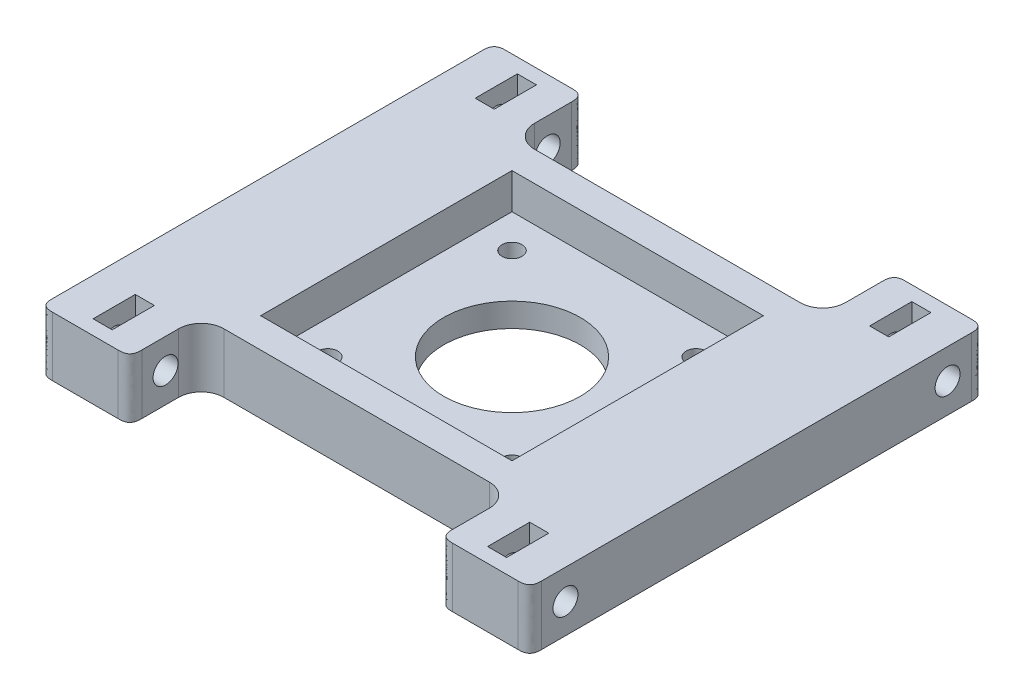
SolidWorks part; units mm, degrees
ref_plane "Front Plane" through (0, 0, 0) normal (0, 0, 1) x (1, 0, 0)
ref_plane "Top Plane" through (0, 0, 0) normal (0, 1, 0) x (1, 0, 0)
ref_plane "Right Plane" through (0, 0, 0) normal (1, 0, 0) x (0, 0, -1)
sketch "Sketch1" plane through (0, 0, 0) normal (0, 1, 0) x (1, 0, 0)
  line L0 (0, 0) -> (19.6051, 0) construction
  line L1 (-21.15, 21.15) -> (21.15, 21.15)
  line L2 (-21.15, 21.15) -> (-21.15, -21.15)
  line L3 (-21.15, -21.15) -> (21.15, -21.15)
  line L4 (21.15, 21.15) -> (21.15, -21.15)
  line L5 (-21.15, 21.15) -> (21.15, -21.15) construction
  line L6 (-21.15, -21.15) -> (21.15, 21.15) construction
  line L8 (-26.15, -26.15) -> (-26.15, 26.15)
  line L9 (-26.15, 26.15) -> (26.15, 26.15)
  line L10 (26.15, 26.15) -> (26.15, -26.15)
  line L11 (26.15, -26.15) -> (-26.15, -26.15)
  circle A0 centre (-15.5, 15.5) radius 1.7
  circle A1 centre (15.5, 15.5) radius 1.7
  circle A2 centre (15.5, -15.5) radius 1.7
  circle A3 centre (-15.5, -15.5) radius 1.7
  circle A4 centre (0, 0) radius 11.5
  point P0 (0, 0)
  point P20 (0, 0)
  point P24 (0, 0)
  point P25 (0, 0)
  point P26 (0, 0)
  point P27 (0, 0)
  point P28 (0, 0)
  point P29 (0, 0)
  dimension "D3" = 3.4
  dimension "D4" = 3.4
  dimension "D5" = 31
  dimension "D6" = 5
  dimension "D9" = 23
  dimension "D1" = 42.3
  dimension "D2" = 5
  dimension "D8" = 5
  dimension "D10" = 5
extrude "Boss-Extrude1" add sketch "Sketch1" along normal blind 4 contours L4 L1 L2 L3 A2 A1 A0 A3 region at (0, 0, -20.5518)
extrude "Boss-Extrude2" add sketch "Sketch1<4>" along normal blind 10 contours L2 L1 L4 L3 | L8 L9 L10 L11
sketch "Sketch1<4>" plane through (0, 0, 0) normal (0, 1, 0) x (1, 0, 0) same geometry as "Sketch1"
sketch "Sketch3" plane through (0, 0, 0) normal (1, 0, 0) x (0, 0, -1)
  line L0 (-26.15, 0) -> (26.15, 0) construction
  line L5 (-38.15, 10) -> (38.15, 10)
  line L6 (-38.15, 10) -> (-38.15, 0)
  line L7 (-38.15, 0) -> (38.15, 0)
  line L8 (38.15, 10) -> (38.15, 0)
  line L11 (26.15, 10) -> (26.15, 0) construction
  line L12 (-26.15, 10) -> (-26.15, 0) construction
  dimension "D1" = 12
  dimension "D2" = 12
extrude "Boss-Extrude3" add sketch "Sketch3" along normal blind 15 from surface starting at face at (26.15, 5, 0)
extrude "Boss-Extrude6" add sketch "Sketch3<3>" against normal blind 15 from surface starting at face at (-26.15, 5, 0)
sketch "Sketch3<3>" plane through (0, 0, 0) normal (1, 0, 0) x (0, 0, -1) same geometry as "Sketch3"
fillet "Fillet1" radius 3.8 4 edges at (26.15, 5, -26.15) (26.15, 5, 26.15) (-26.15, 5, 26.15) (-26.15, 5, -26.15)
sketch "Sketch4" plane through (0, 0, 0) normal (1, 0, 0) x (0, 0, -1)
  line L0 (0, 0) -> (0, -25.7423) construction
  circle A0 centre (-32.15, 5) radius 2.1
  circle A1 centre (32.15, 5) radius 2.1
  dimension "D1" = 4.2
  dimension "D2" = 5
  dimension "D3" = 6
extrude "Cut-Extrude1" cut sketch "Sketch4" against normal through all both and the other way through all
sketch "Sketch6" plane through (0, 0, 0) normal (0, 1, 0) x (1, 0, 0)
  line L0 (0, -1000) -> (0, 49000) construction
  line L1 (-34.7958, 35.7) -> (-31.5842, 35.7)
  line L2 (-34.7958, 35.7) -> (-34.7958, 28.6)
  line L3 (-34.7958, 28.6) -> (-31.5842, 28.6)
  line L4 (-31.5842, 35.7) -> (-31.5842, 28.6)
  line L5 (-34.7958, 35.7) -> (-31.5842, 28.6) construction
  line L6 (-34.7958, 28.6) -> (-31.5842, 35.7) construction
  line L7 (-26.15, 38.15) -> (-26.15, 29.95) construction
  line L8 (-1000, 0) -> (49000, 0) construction
  line L10 (-34.7958, -28.6) -> (-31.5842, -35.7) construction
  line L11 (-34.7958, -35.7) -> (-31.5842, -28.6) construction
  line L12 (-31.5842, -35.7) -> (-31.5842, -28.6)
  line L13 (-34.7958, -28.6) -> (-31.5842, -28.6)
  line L14 (-34.7958, -35.7) -> (-34.7958, -28.6)
  line L15 (-34.7958, -35.7) -> (-31.5842, -35.7)
  line L16 (34.7958, -35.7) -> (31.5842, -28.6) construction
  line L17 (34.7958, -28.6) -> (31.5842, -35.7) construction
  line L18 (34.7958, 28.6) -> (31.5842, 35.7) construction
  line L19 (34.7958, 35.7) -> (31.5842, 28.6) construction
  line L20 (34.7958, -35.7) -> (31.5842, -35.7)
  line L21 (34.7958, -35.7) -> (34.7958, -28.6)
  line L22 (34.7958, -28.6) -> (31.5842, -28.6)
  line L23 (31.5842, -35.7) -> (31.5842, -28.6)
  line L24 (31.5842, 35.7) -> (31.5842, 28.6)
  line L25 (34.7958, 28.6) -> (31.5842, 28.6)
  line L26 (34.7958, 35.7) -> (34.7958, 28.6)
  line L27 (34.7958, 35.7) -> (31.5842, 35.7)
  point P0 (-33.19, 32.15)
  point P17 (-33.19, -32.15)
  point P26 (33.19, -32.15)
  point P27 (33.19, 32.15)
  dimension "D1" = 7.1
  dimension "D2" = 7.04
extrude "Cut-Extrude2" cut sketch "Sketch6" against normal blind 9.12 from surface starting at face at (0, 10, 0)
fillet "Fillet2" radius 2 8 edges at (-26.15, 5, -38.15) (26.15, 5, -38.15) (41.15, 5, -38.15) (41.15, 5, 38.15) (26.15, 5, 38.15) (-26.15, 5, 38.15) (-41.15, 5, 38.15) (-41.15, 5, -38.15) curvature continuous yes
